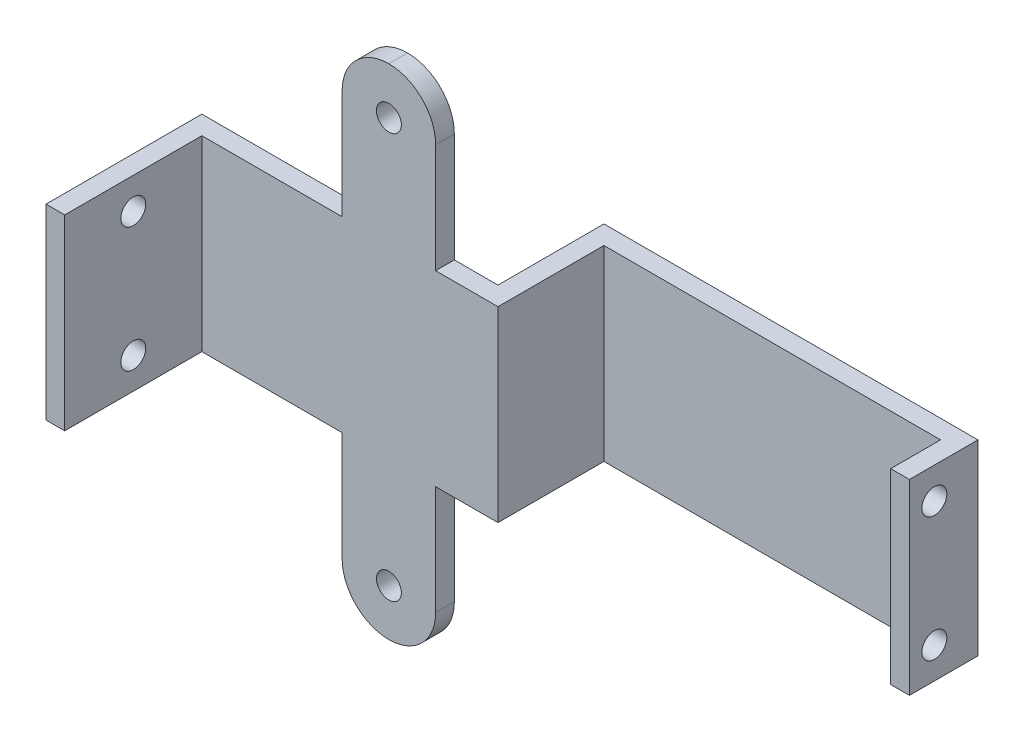
SolidWorks part; units mm, degrees
ref_plane "Front Plane" through (0, 0, 0) normal (0, 0, 1) x (1, 0, 0)
ref_plane "Top Plane" through (0, 0, 0) normal (0, 1, 0) x (1, 0, 0)
ref_plane "Right Plane" through (0, 0, 0) normal (1, 0, 0) x (0, 0, -1)
sketch "Sketch1" plane through (0, 0, 0) normal (0, 1, 0) x (1, 0, 0)
  line L0 (0, 0) -> (-60, 0)
  line L1 (-60, 0) -> (-60, -17)
  line L2 (-60, -17) -> (-107.5, -17)
  line L3 (-107.5, -17) -> (-107.5, -42)
  line L4 (0, -3) -> (-57, -3)
  line L5 (-57, -3) -> (-57, -20)
  line L6 (-57, -20) -> (-104.5, -20)
  line L7 (-104.5, -20) -> (-104.5, -42)
  line L8 (0, 0) -> (0, -3)
  line L9 (-107.5, -42) -> (-104.5, -42)
  dimension "D2" = 60
  dimension "D3" = 17
  dimension "D4" = 25
  dimension "D5" = 47.5
  dimension "D1" = 3
extrude "Boss-Extrude1" add sketch "Sketch1" along normal blind 30
sketch "Sketch2" plane through (-104.5, 0, 0) normal (1, 0, 0) x (0, 0, -1)
  line L0 (-31, 30) -> (-31, 0) construction
  line L1 (-42, 30) -> (-20, 30) construction
  line L2 (-42, 0) -> (-20, 0) construction
  circle A0 centre (-31, 25) radius 2
  circle A1 centre (-31, 5) radius 2
  dimension "D1" = 4
  dimension "D2" = 4
  dimension "D4" = 5
  dimension "D3" = 20
extrude "Cut-Extrude1" cut sketch "Sketch2" against normal up to surface (3 mm away) up to face at (-107.5, 15, 29.5)
sketch "Sketch4" plane through (0, 0, 0) normal (1, 0, 0) x (0, 0, -1)
  line L0 (-20, 0) -> (-3, 0) construction
  line L1 (-3, 30) -> (-11, 30)
  line L2 (-3, 30) -> (-3, 0)
  line L3 (-3, 0) -> (-11, 0)
  line L4 (-11, 30) -> (-11, 0)
  circle A0 centre (-7, 25) radius 2
  circle A1 centre (-7, 5) radius 2
  circle A2 centre (-31, 25) radius 2 construction
  dimension "D2" = 5
  dimension "D1" = 8
  dimension "D3" = 20
  dimension "D4" = 4
extrude "Boss-Extrude2" add sketch "Sketch4" against normal blind 3
sketch "Sketch5" plane through (0, 0, 20) normal (0, 0, 1) x (1, 0, 0)
  line L1 (-82, -25) -> (-67, -25)
  line L2 (-82, -25) -> (-82, 55)
  line L3 (-82, 55) -> (-67, 55)
  line L4 (-67, -25) -> (-67, 55)
  line L5 (-82, -25) -> (-67, 55) construction
  line L6 (-82, 55) -> (-67, -25) construction
  line L7 (-104.5, 0) -> (-57, 0) construction
  line L8 (-57, 30) -> (-57, 0) construction
  point P0 (-74.5, 15)
  dimension "D1" = 15
  dimension "D2" = 80
  dimension "D3" = 15
  dimension "D4" = 10
extrude "Boss-Extrude3" add sketch "Sketch5" against normal blind 3
fillet "Fillet1" radius 7.5 4 edges at (-67, -25, 18.5) (-82, -25, 18.5) (-82, 55, 18.5) (-67, 55, 18.5)
sketch "Sketch6" plane through (0, 0, 20) normal (0, 0, 1) x (1, 0, 0)
  circle A0 centre (-74.5, 47.5) radius 2
  circle A1 centre (-74.5, -17.5) radius 2
  dimension "D1" = 4
  dimension "D2" = 4
extrude "Cut-Extrude2" cut sketch "Sketch6" against normal blind 3
